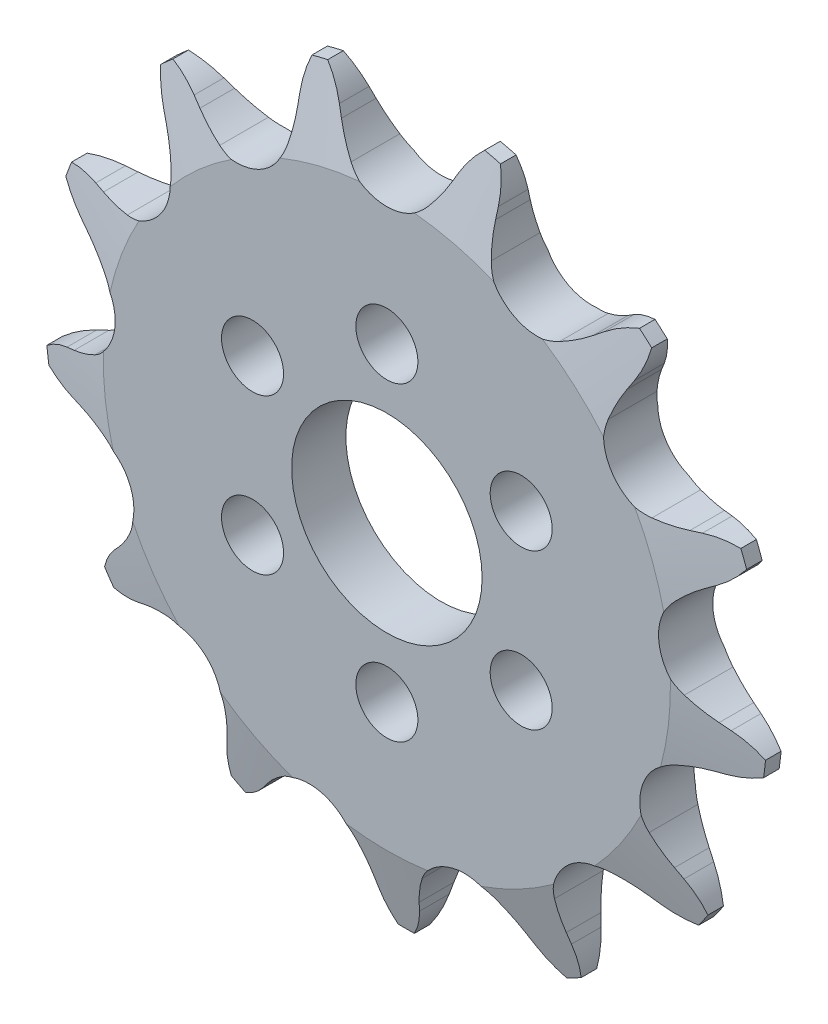
SolidWorks part; units mm, degrees
material "AISI 4130 Steel, annealed at 865C"
ref_plane "Front Plane" through (0, 0, 0) normal (0, 0, 1) x (1, 0, 0)
ref_plane "Top Plane" through (0, 0, 0) normal (0, 1, 0) x (1, 0, 0)
ref_plane "Right Plane" through (0, 0, 0) normal (1, 0, 0) x (0, 0, -1)
sketch "Sketch0" plane through (0, 0, 0) normal (0, 0, 1) x (1, 0, 0)
  line L0 (7.9375, -32.2037) -> (0, 0) construction
  line L1 (0, 0) -> (21.9941, -24.8262) construction
  line L2 (0, 0) -> (-7.9375, -32.2037) construction
  line L3 (7.9375, -32.2037) -> (21.9941, -24.8262) construction
  line L4 (7.9375, -32.2037) -> (-7.9375, -32.2037) construction
  line L5 (13.9545, -31.0679) -> (13.2815, -30.2592)
  line L6 (7.9375, -32.2037) -> (0, -34.1601) construction
  line L7 (2.0819, -33.9942) -> (2.302, -32.9654)
  line L8 (0, -32.2037) -> (0, -36.9662) construction
  line L9 (10.986, -28.0897) -> (3.0984, -38.7342) construction
  line L10 (0, 0) -> (0, -32.2037) construction
  line L11 (13.2815, -30.2592) -> (3.0984, -38.7342) construction
  line L12 (0, -36.9662) -> (0, -38.0102) construction
  line L13 (20.5322, -25.5935) -> (13.9545, -31.0679) construction
  circle A0 centre (0, 0) radius 36.9662 construction
  circle A1 centre (0, 0) radius 33.1675 construction
  arc A2 (-7.9261, -40.603) -> (25.8874, -32.2687) centre (0, 0) ccw
  circle A3 centre (0, 0) radius 38.0102 construction
  circle A4 centre (7.9375, -32.2037) radius 5.08 construction
  arc A7 (10.986, -28.0897) -> (3.3263, -29.9776) centre (7.9375, -32.2037) ccw
  circle A8 centre (7.9375, -32.2037) radius 5.1204 construction
  arc A9 (13.9545, -31.0679) -> (25.8874, -32.2687) centre (20.5322, -25.5935) ccw
  arc A10 (13.2815, -30.2592) -> (10.986, -28.0897) centre (3.0984, -38.7342) ccw
  arc A11 (2.0819, -33.9942) -> (-7.9261, -40.603) centre (-6.2865, -32.2037) cw
  arc A12 (2.302, -32.9654) -> (3.3263, -29.9776) centre (15.2572, -35.7373) cw
  dimension "D1" = 5.1204
  dimension "R" = 5.1204
sketch "Sketch1" plane through (0, 0, 0) normal (1, 0, 0) x (0, 0, -1)
  line L0 (2.7781, 0) -> (-2.7781, 0)
  line L1 (-2.7781, 0) -> (-2.7781, 29.0287)
  line L2 (-2.7781, 29.0287) -> (-0.7937, 36.9662)
  line L3 (-0.7937, 36.9662) -> (0.7937, 36.9662)
  line L4 (0.7937, 36.9662) -> (2.7781, 29.0287)
  line L5 (2.7781, 29.0287) -> (2.7781, 0)
  line L7 (0, 36.9662) -> (0, 0) construction
  line L8 (-2.7781, 29.0287) -> (2.7781, 29.0287) construction
  line L9 (0, 36.9662) -> (0, -36.9662) construction
  line L10 (-2.7781, 29.0287) -> (-2.7781, 36.9662) construction
  line L11 (-2.7781, 36.9662) -> (-0.7937, 36.9662) construction
  line L12 (0.7937, 36.9662) -> (2.7781, 36.9662) construction
  line L13 (2.7781, 36.9662) -> (2.7781, 29.0287) construction
revolve "Revolve1" add sketch "Sketch1" angle 360 mid plane about L0
extrude "Cut-Extrude1" cut sketch "Sketch0" against normal through all and the other way through all
pattern_circular "CirPattern1" count 13 over 360 about axis through (0, 0, -2.7781) along (0, 0, -1) of "Cut-Extrude1"
sketch "Sketch2" plane through (0, 0, 0) normal (0, 0, 1) x (1, 0, 0)
  circle A0 centre (0, 0) radius 7.9375 construction
  circle A1 centre (0, 0) radius 30.1625
  circle A2 centre (0, 0) radius 36.957 construction
  dimension "Bore" = 15.875
  dimension "Hub Dia." = 60.325
  dimension "OD" = 73.914
sketch "Sketch3" plane through (0, 0, 0) normal (0, 0, 1) x (1, 0, 0)
  circle A1 centre (0, 0) radius 9.75
  circle A2 centre (0, 0) radius 36.957 construction
  circle A3 centre (0, 0) radius 36.957
extrude "Cut-Extrude2" cut sketch "Sketch3" along normal through all and the other way through all flip side to cut
sketch "Sketch4" plane through (0, 0, -2.7781) normal (0, 0, -1) x (-1, 0, 0)
  line L0 (0, 0) -> (0, 15.875) construction
  circle A0 centre (0, 15.875) radius 3.175
  circle A1 centre (13.7482, 7.9375) radius 3.175
  circle A2 centre (13.7482, -7.9375) radius 3.175
  circle A3 centre (0, -15.875) radius 3.175
  circle A4 centre (-13.7482, -7.9375) radius 3.175
  circle A5 centre (-13.7482, 7.9375) radius 3.175
  point P17 (0, 0)
  dimension "D1" = 6
extrude "Cut-Extrude3" cut sketch "Sketch4" against normal through all
sketch "Sketch5" plane through (0, 0, 2.7781) normal (0, 0, 1) x (1, 0, 0)
  line L0 (0, 0) -> (9.75, 0) construction
  line L1 (9.75, 0) -> (11, 0) construction
  circle A0 centre (0, 0) radius 11 construction
  circle A1 centre (0, 0) radius 9.75 construction
sketch "Sketch6" plane through (0, 0, -2.7781) normal (0, 0, -1) x (-1, 0, 0)
  circle A0 centre (0, 0) radius 28.024 construction
  circle A1 centre (0, 0) radius 24.2521 construction
ref_plane "Plane1" through (-29.6883, 20.4924, 0) normal (-0.823, 0.5681, 0) x (0, 0, 1)
ref_plane "Plane2" through (-35.811, 4.3482, 0) normal (-0.9927, 0.1205, 0) x (0, 0, 1)
ref_plane "Plane3" through (-33.7298, -12.792, 0) normal (-0.935, -0.3546, 0) x (0, 0, 1)
ref_plane "Plane4" through (-23.9215, -27.0018, 0) normal (-0.6631, -0.7485, 0) x (-0.7485, 0.6631, 0)
ref_plane "Plane5" through (-8.6331, -35.0258, 0) normal (-0.2393, -0.9709, 0) x (-0.9709, 0.2393, 0)
sketch "Sketch7" plane through (-29.6883, 20.4924, 0) normal (-0.823, 0.5681, 0) x (0, 0, 1)
  line L0 (-6.5106, 0) -> (7.7601, 0)
sketch "Sketch8" plane through (-35.811, 4.3482, 0) normal (-0.9927, 0.1205, 0) x (0, 0, 1)
  line L0 (-7.786, 0) -> (10.2102, 0)
sketch "Sketch9" plane through (-33.7298, -12.792, 0) normal (-0.935, -0.3546, 0) x (0, 0, 1)
  line L0 (-7.6671, 0) -> (14.0341, 0)
  line L1 (-2.7781, 0) -> (2.7781, 0) construction
sketch "Sketch10" plane through (-23.9215, -27.0018, 0) normal (-0.6631, -0.7485, 0) x (-0.7485, 0.6631, 0)
  line L0 (0, -3.5829) -> (0, 5.4944)
sketch "Sketch11" plane through (-8.6331, -35.0258, 0) normal (-0.2393, -0.9709, 0) x (-0.9709, 0.2393, 0)
  line L0 (0, -5.4358) -> (0, 8.5188)
split line "Split Line7"
split line "Split Line8"
split line "Split Line9"
split line "Split Line10"
split line "Split Line11"
ref_plane "Plane6" through (0, 0, 0) normal (0, 0, 1) x (1, 0, 0)
equation "\"360/N@Sketch0\" = 360/\"Teeth@CirPattern1\""
equation "\"Ds@Sketch0\" = 1.005 * \"Dr@Sketch0\" + 0.003"
equation "\"R@Sketch0\" = 1/2 * \"Ds@Sketch0\""
equation "\"A@Sketch0\" = 35 +  ( 60 / \"Teeth@CirPattern1\" ) "
equation "\"B@Sketch0\" = 18 -  ( 56 / \"Teeth@CirPattern1\" )"
equation "\"ac@Sketch0\" = 0.8 * \"Dr@Sketch0\""
equation "\"ab@Sketch0\" = 1.4 * \"Dr@Sketch0\""
equation "\"J@Sketch0\" = 0.3 * \"Pitch@Sketch0\""
equation "\"h@Sketch1\" = \"Pitch@Sketch0\" / 2"
equation "\"g@Sketch1\" = \"h@Sketch1\" / 4"
